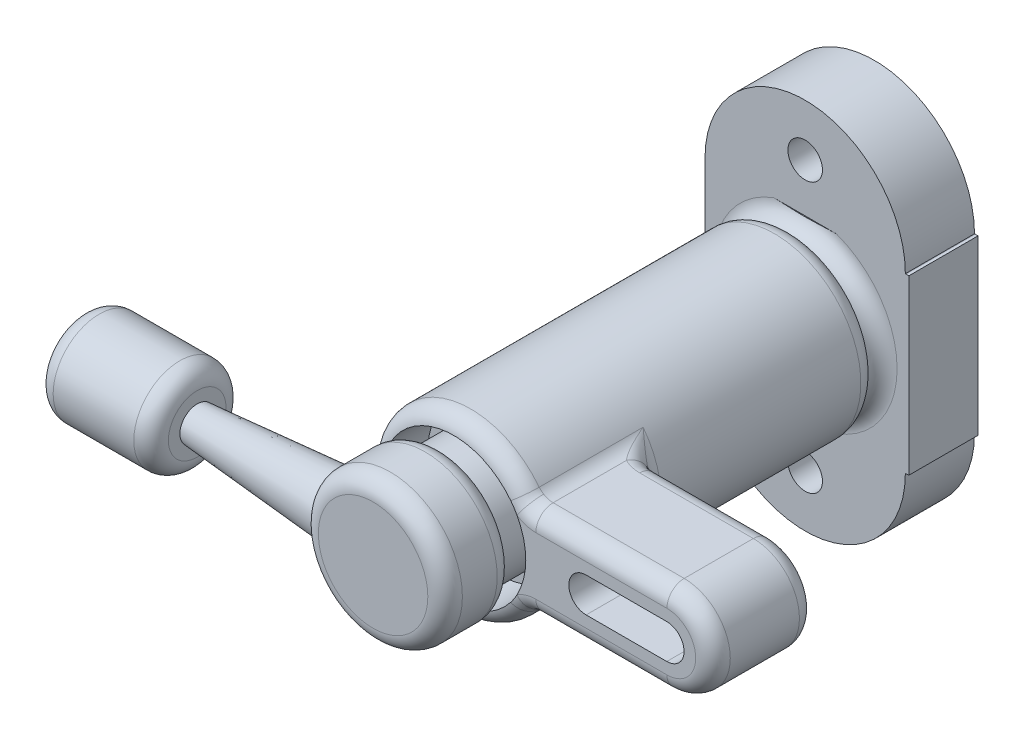
SolidWorks part; units mm, degrees
material "Plain Carbon Steel"
ref_plane "Front Plane" through (0, 0, 0) normal (0, 0, 1) x (1, 0, 0)
ref_plane "Top Plane" through (0, 0, 0) normal (0, 1, 0) x (1, 0, 0)
ref_plane "Right Plane" through (0, 0, 0) normal (1, 0, 0) x (0, 0, -1)
sketch "base" plane through (0, 0, 0) normal (0, 0, 1) x (1, 0, 0)
  line L0 (0, 0) -> (35, 0) construction
  line L1 (0, 15) -> (35, 15)
  line L2 (0, -15) -> (35, -15)
  line L3 (17.5, -20.0972) -> (17.5, 19.9979) construction
  arc A0 (0, 15) -> (0, -15) centre (0, 0) ccw
  arc A1 (35, -15) -> (35, 15) centre (35, 0) ccw
  circle A2 centre (-7.5, 0) radius 3
  circle A3 centre (42.5, 0) radius 3
  point P3 (17.5, 0)
  point P8 (-15, 0)
  point P9 (50, 0)
  dimension "D3" = 25
  dimension "D1" = 65
  dimension "D2" = 30
extrude "Boss-Extrude1" add sketch "base" along normal blind 12
sketch "Sketch4" plane through (0, 0, 12) normal (0, 0, 1) x (1, 0, 0)
  circle A0 centre (17.5, 0) radius 13
extrude "Boss-Extrude2" add sketch "Sketch4" along normal blind 2.5
fillet "Fillet5" radius 3 1 edges at (30.5, 0, 12)
sketch "Sketch6" plane through (0, 0, 14.5) normal (0, 0, 1) x (1, 0, 0)
  circle A0 centre (17.5, 0) radius 15
extrude "Boss-Extrude3" add sketch "Sketch6" along normal blind 40.5
fillet "Fillet6" radius 3 1 edges at (32.5, 0, 14.5)
ref_plane "Plane1" through (0, 0, 55) normal (0, 0, 1) x (1, 0, 0)
sketch "Sketch7" plane through (0, 0, 55) normal (0, 0, 1) x (1, 0, 0)
  line L0 (30.1886, -8) -> (54.5, -8)
  line L1 (-38.0651, 0) -> (51.9349, 0) construction
  line L2 (54.4765, 0) -> (40.4765, 0) construction
  line L3 (54.5, 8) -> (30.1886, 8)
  line L4 (54.4765, -3) -> (40.4765, -3)
  line L5 (54.4765, 3) -> (40.4765, 3)
  arc A0 (30.1886, 8) -> (30.1886, -8) centre (17.5, 0) ccw
  arc A1 (54.5, 8) -> (54.5, -8) centre (54.5, 0) cw
  arc A2 (54.4765, -3) -> (54.4765, 3) centre (54.4765, 0) ccw
  arc A3 (40.4765, 3) -> (40.4765, -3) centre (40.4765, 0) ccw
  point P6 (17.5, 0)
  point P10 (62.5, 0)
  point P13 (47.4765, 0)
  dimension "D1" = 16
  dimension "D4" = 3
  dimension "D2" = 8
  dimension "D3" = 45
extrude "Boss-Extrude4" add sketch "Sketch7" along normal blind 18
fillet "Fillet7" radius 3 1 edges at (32.5, 0, 55)
fillet "Fillet8" radius 3 2 edges at (30.1886, -8, 62.5) (30.1886, 8, 62.5)
fillet "Fillet9" radius 3 7 edges at (30.5544, -8.2476, 53.5666) (32.4684, -8, 54.8184) (30.5544, 8.2476, 53.5666) (32.3776, 8, 54.7879) (44.0623, -8, 55) (62.5, 0, 55) (44.0623, 8, 55)
sketch "Sketch8" plane through (0, 0, 73) normal (0, 0, 1) x (1, 0, 0)
  circle A0 centre (17.5, 0) radius 12.5
extrude "Cut-Extrude1" cut sketch "Sketch8" against normal blind 8
sketch "Sketch9" plane through (0, 0, 65) normal (0, 0, 1) x (1, 0, 0)
  circle A0 centre (17.5, 0) radius 10
extrude "Boss-Extrude5" add sketch "Sketch9" along normal blind 22
sketch "Sketch10" plane through (0, 0, 87) normal (0, 0, 1) x (1, 0, 0)
  circle A0 centre (17.5, 0) radius 12.5
extrude "Boss-Extrude6" add sketch "Sketch10" against normal blind 12
fillet "Fillet10" radius 3 5 edges at (30.4249, -8.3074, 73) (30.4249, 8.3074, 73) (62.5, 0, 73) (43.1239, -8, 73) (43.1239, 8, 73)
fillet "Fillet11" radius 3 1 edges at (30, 0, 75)
fillet "Fillet12" radius 3 1 edges at (30, 0, 87)
sketch "Sketch11" plane through (0, 0, 87) normal (0, 0, 1) x (1, 0, 0)
  circle A0 centre (17.5, 0) radius 3
ref_plane "Plane2" through (6, 0, 0) normal (1, 0, 0) x (0, 0, -1)
sketch "Sketch13" plane through (6, 0, 0) normal (1, 0, 0) x (0, 0, -1)
  circle A0 centre (-81.0356, 0) radius 5
ref_plane "Plane4" through (-19, 0, 0) normal (1, 0, 0) x (0, 0, -1)
sketch "Sketch14" plane through (-19, 0, 0) normal (1, 0, 0) x (0, 0, -1)
  circle A0 centre (-81.0356, 0) radius 3
loft "Loft1" add profiles "Sketch13", "Sketch14" connector at (6, 0, 76.0356) connector at (-19, 0, 78.0356)
sketch "Sketch15" plane through (-19, 0, 0) normal (-1, 0, 0) x (0, 0, 1)
  circle A0 centre (81.0356, 0) radius 8
extrude "Boss-Extrude7" add sketch "Sketch15" along normal blind 20
fillet "Fillet14" radius 3 2 edges at (-19, 0, 89.0356) (-39, 0, 89.0356)
sketch "Sketch16" plane through (0, 0, 0) normal (0, 0, 1) x (1, 0, 0)
  line L0 (17.5, 15) -> (17.5, -15) construction
  line L1 (35, 15) -> (0, 15) construction
  line L2 (0, -15) -> (35, -15) construction
  line L3 (34.8918, 15) -> (34.8918, -15)
  line L4 (0.1082, 15) -> (0.1082, -15)
  line L5 (25.0353, 0) -> (8.29, 0) construction
  arc A0 (34.8918, 15) -> (0.1082, 15) centre (17.5, 15) ccw
  arc A1 (0.1082, -15) -> (34.8918, -15) centre (17.5, -15) ccw
  circle A2 centre (17.5, 23.3981) radius 3
  circle A3 centre (17.5, -23.3981) radius 3
  point P6 (17.5, 0)
extrude "Boss-Extrude8" add sketch "Sketch16" along normal up to surface (12 mm away) up to face at (35.351, 0, 12)
sketch "Sketch17" plane through (0, 0, 0) normal (0, 0, -1) x (-1, 0, 0)
  line L1 (-0.1082, -34.5373) -> (-35.4993, -34.5373)
  line L2 (-0.1082, -34.5373) -> (-0.1082, 33.2956)
  line L3 (-0.1082, 33.2956) -> (-35.4993, 33.2956)
  line L4 (-35.4993, -34.5373) -> (-35.4993, 33.2956)
extrude "Cut-Extrude-Thin1" cut sketch "Sketch17" against normal up to surface (12 mm away) thin up to face at (17.5, 0, 12) thin type one direction wall 10
